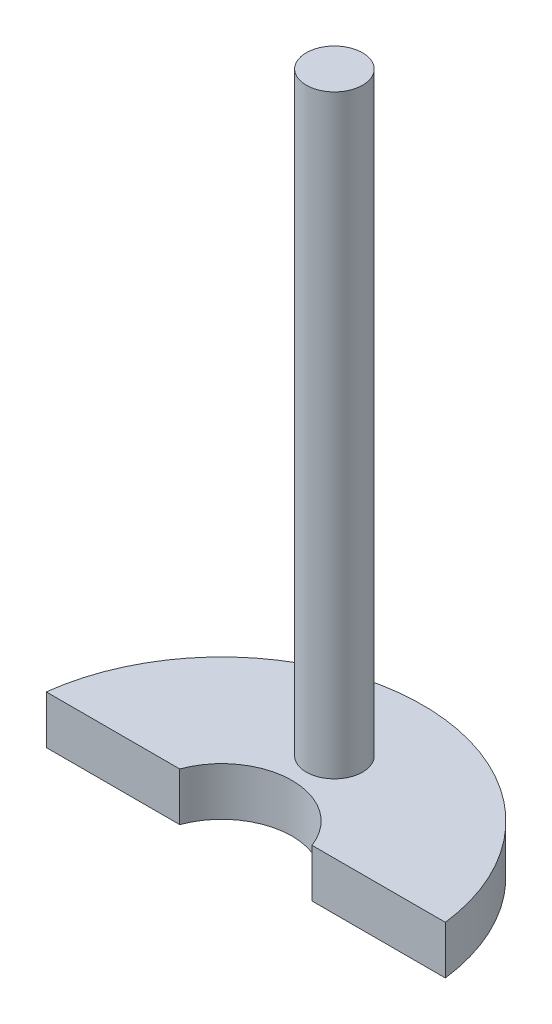
SolidWorks part; units mm, degrees
ref_plane "Front Plane" through (0, 0, 0) normal (0, 0, 1) x (1, 0, 0)
ref_plane "Top Plane" through (0, 0, 0) normal (0, 1, 0) x (1, 0, 0)
ref_plane "Right Plane" through (0, 0, 0) normal (1, 0, 0) x (0, 0, -1)
sketch "Sketch11" plane through (0, 0, 0) normal (0, 1, 0) x (1, 0, 0)
  line L0 (0, 0) -> (0, -7.0111) construction
  line L1 (0, 0) -> (0, 7.0111) construction
  line L2 (0, 8.7611) -> (1.5729, 8.7611) construction
  line L3 (0, 8.7611) -> (-1.5729, 8.7611) construction
  line L4 (7.0293, 0) -> (7.0293, 1.5) construction
  line L5 (-12.4097, 1.5) -> (12.4097, 1.5)
  line L6 (-12.5, 0) -> (12.5, 0) construction
  line L13 (-12.5, 0) -> (12.5, 0)
  circle A0 centre (0, 0) radius 12.5
  arc A1 (-2.9783, 12.14) -> (2.9783, 12.14) centre (0, 12.5) ccw construction
  arc A2 (2.9783, -12.14) -> (-2.9783, -12.14) centre (0, -12.5) ccw construction
  circle A3 centre (0, 0) radius 4.375
  circle A4 centre (0, 7.0111) radius 1.75
  circle A5 centre (0, -7.0111) radius 1.75
  dimension "D1" = 25
  dimension "D2" = 6
  dimension "D3" = 8.75
  dimension "D4" = 3.5
  dimension "D5" = 7.0111
  dimension "D6" = 1.5
extrude "BasePlateV2" add sketch "Sketch11" along normal blind 3 contours A3 L5 A0 A4 | A4 region at (0, 0, -12.2285) region at (0, 0, -7.0111)
extrude "RodV2" add sketch "Sketch11<14>" along normal blind 40 contours A4 region at (0, 0, -7.0111)
sketch "Sketch11<14>" plane through (0, 0, 0) normal (0, 1, 0) x (1, 0, 0) same geometry as "Sketch11"
